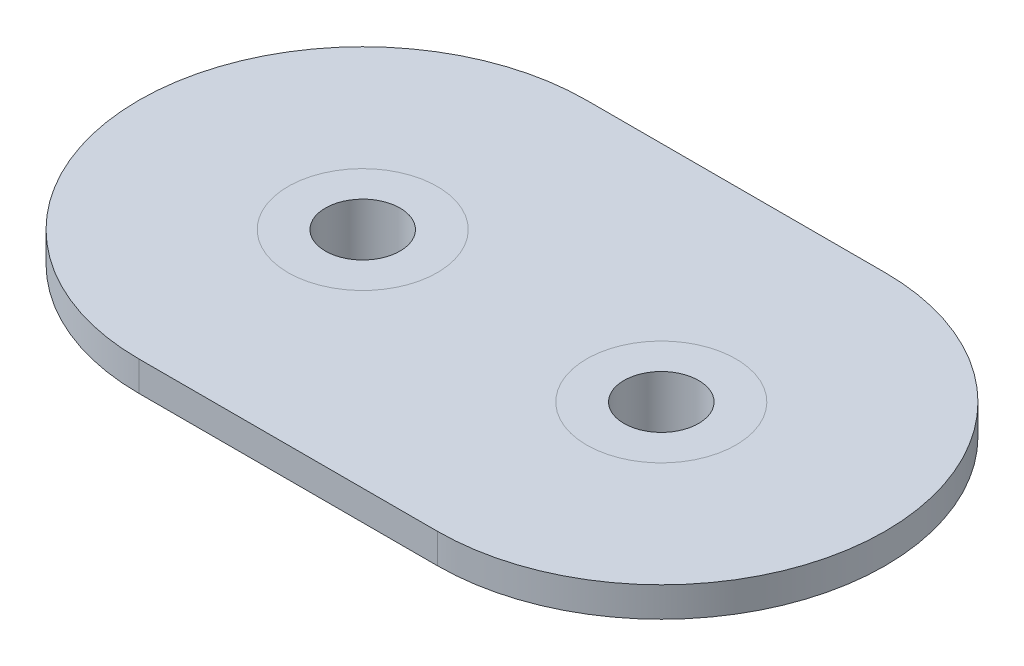
SolidWorks part; units mm, degrees
ref_plane "Front Plane" through (0, 0, 0) normal (0, 0, 1) x (1, 0, 0)
ref_plane "Top Plane" through (0, 0, 0) normal (0, 1, 0) x (1, 0, 0)
ref_plane "Right Plane" through (0, 0, 0) normal (1, 0, 0) x (0, 0, -1)
sketch "Sketch1" plane through (0, 0, 0) normal (0, 1, 0) x (1, 0, 0)
  line L0 (-10, 0) -> (10, 0) construction
  line L1 (-10, 15) -> (10, 15)
  line L2 (-10, -15) -> (10, -15)
  arc A0 (-10, 15) -> (-10, -15) centre (-10, 0) ccw
  arc A1 (10, -15) -> (10, 15) centre (10, 0) ccw
  circle A2 centre (-10, 0) radius 5
  circle A3 centre (10, 0) radius 5
  circle A4 centre (-10, 0) radius 2.5
  circle A5 centre (10, 0) radius 2.5
  point P2 (0, 0)
  dimension "D2" = 10
  dimension "D3" = 10
  dimension "D5" = 5
  dimension "D6" = 5
  dimension "D1" = 20
  dimension "D4" = 30
extrude "Boss-Extrude1" add sketch "Sketch1" along normal blind 2 contours L2 A1 L1 A0 A2 A3 region at (0, 0, 0)
extrude "Boss-Extrude2" add sketch "Sketch1<3>" against normal blind 6 and the other way blind 2 separate body contours A3 A5 | A4 A2 region at (-14.8586, 0, 0) region at (5.1414, 0, 0)
sketch "Sketch1<3>" plane through (0, 0, 0) normal (0, 1, 0) x (1, 0, 0) same geometry as "Sketch1"
